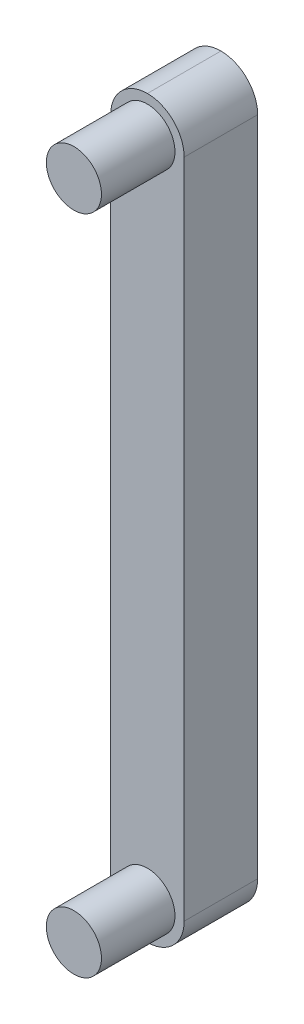
SolidWorks part; units mm, degrees
ref_plane "Front Plane" through (0, 0, 0) normal (0, 0, 1) x (1, 0, 0)
ref_plane "Top Plane" through (0, 0, 0) normal (0, 1, 0) x (1, 0, 0)
ref_plane "Right Plane" through (0, 0, 0) normal (1, 0, 0) x (0, 0, -1)
sketch "Sketch1" plane through (0, 0, 0) normal (0, 0, 1) x (1, 0, 0)
  line L1 (0, 0) -> (20, 0)
  line L2 (0, 0) -> (0, 200)
  line L3 (0, 200) -> (20, 200)
  line L4 (20, 0) -> (20, 200)
  dimension "D1" = 200
  dimension "D2" = 20
extrude "Boss-Extrude1" add sketch "Sketch1" along normal blind 20
fillet "Fillet1" radius 10 1 edges at (20, 200, 10) type face fillet first side face at (0, 100, 10) first side face at (10, 200, 10) second side face at (20, 100, 10)
fillet "Fillet2" radius 10 1 edges at (0, 200, 10) type face fillet first side face at (0, 100, 10) second side face at (5, 200, 10)
fillet "Fillet3" radius 10 1 edges at (0, 0, 10) type face fillet first side face at (0, 95, 10) second side face at (10, 0, 10)
fillet "Fillet4" radius 10 1 edges at (20, 0, 10) type face fillet first side face at (15, 0, 10) second side face at (20, 95, 10)
scale "Scale1" bodies to scale 106 103 scale about centroid uniform scaling yes scale factor 0.8
sketch "Sketch2" plane through (0, 0, 18) normal (0, 0, 1) x (1, 0, 0)
  circle A0 centre (10, 172) radius 6
  circle A1 centre (10, 28) radius 6
  dimension "D1" = 12
  dimension "D2" = 12
extrude "Boss-Extrude3" add sketch "Sketch2" along normal blind 16
